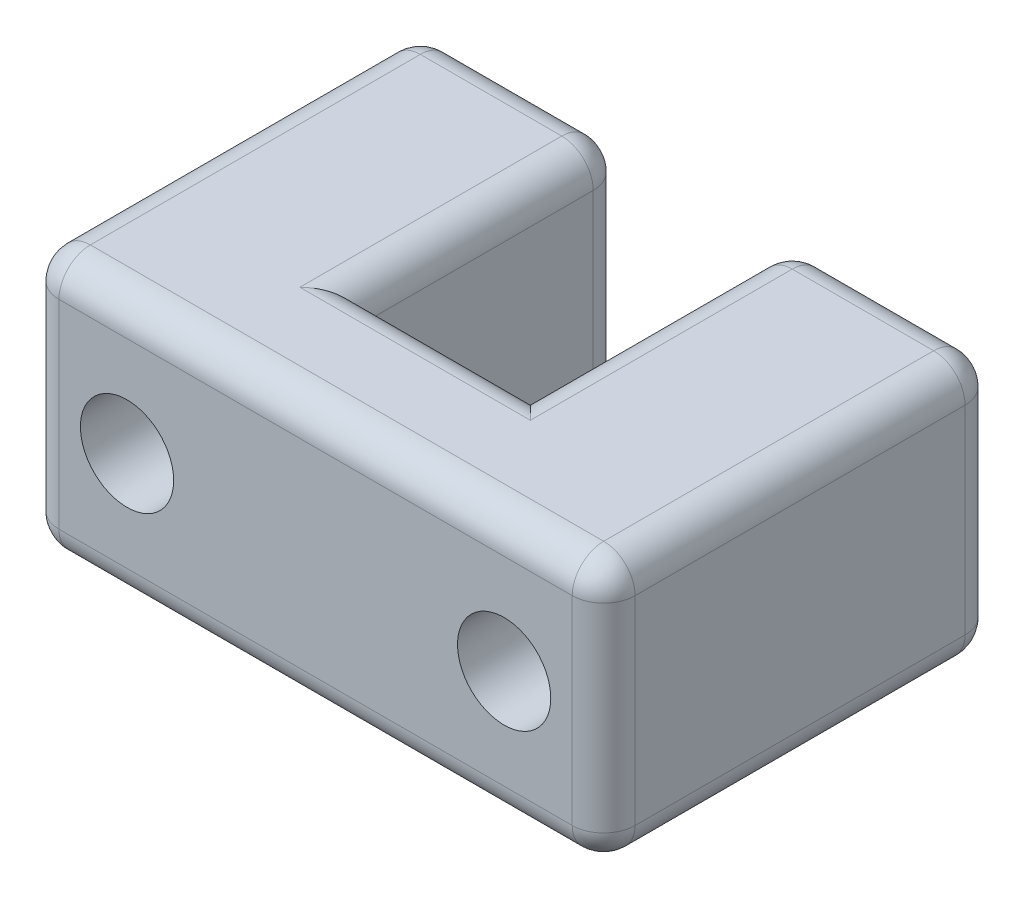
SolidWorks part; units mm, degrees
ref_plane "Front" through (0, 0, 0) normal (0, 0, 1) x (1, 0, 0)
ref_plane "Top" through (0, 0, 0) normal (0, 1, 0) x (1, 0, 0)
ref_plane "Right" through (0, 0, 0) normal (1, 0, 0) x (0, 0, -1)
sketch "Sketch1" plane through (0, 0, 0) normal (0, 1, 0) x (1, 0, 0)
  line L0 (0, 9.525) -> (4.953, 9.525)
  line L1 (0, 9.525) -> (13.97, 9.525) construction
  line L2 (0, 9.525) -> (0, 0)
  line L3 (0, 0) -> (13.97, 0)
  line L4 (13.97, 9.525) -> (13.97, 0)
  line L5 (4.953, 9.525) -> (4.953, 3.175)
  line L6 (4.953, 3.175) -> (9.017, 3.175)
  line L7 (9.017, 3.175) -> (9.017, 9.525)
  line L8 (9.017, 9.525) -> (13.97, 9.525)
  dimension "D1" = 13.97
  dimension "D2" = 4.064
  dimension "D3" = 6.35
  dimension "D4" = 9.525
extrude "Boss-Extrude1" add sketch "Sketch1" along normal blind 6.35
sketch "Sketch2" plane through (0, 0, 0) normal (0, 0, 1) x (1, 0, 0)
  line L0 (6.985, 6.35) -> (6.985, 0) construction
  line L1 (2.413, 3.175) -> (11.557, 3.175) construction
  line L2 (0, 6.35) -> (13.97, 6.35) construction
  line L3 (0, 0) -> (13.97, 0) construction
  circle A0 centre (2.413, 3.175) radius 1.1303
  circle A1 centre (11.557, 3.175) radius 1.1303
  point P8 (6.985, 3.175)
  dimension "D1" = 9.144
  dimension "D2" = 2.2606
extrude "Cut-Extrude1" cut sketch "Sketch2" against normal up to surface (9.525 mm away) up to face at (11.4935, 3.175, -9.525)
fillet "Fillet1" radius 0.762 22 edges at (2.4765, 6.35, -9.525) (4.953, 6.35, -6.35) (6.985, 6.35, -3.175) (9.017, 6.35, -6.35) (11.4935, 6.35, -9.525) (13.97, 6.35, -4.7625) (6.985, 6.35, 0) (0, 6.35, -4.7625) (6.985, 0, 0) (13.97, 0, -4.7625) (11.4935, 0, -9.525) (9.017, 0, -6.35) (6.985, 0, -3.175) (4.953, 0, -6.35) (2.4765, 0, -9.525) (0, 0, -4.7625) (0, 3.175, -9.525) (0, 3.175, 0) (13.97, 3.175, 0) (13.97, 3.175, -9.525) (4.953, 3.175, -9.525) (9.017, 3.175, -9.525)
